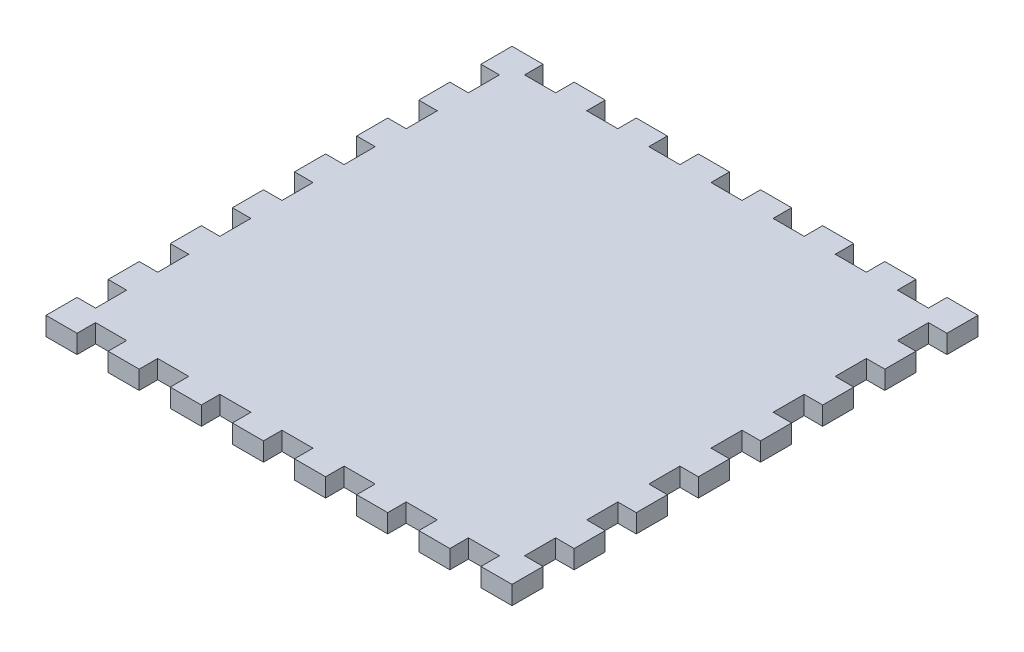
SolidWorks part; units mm, degrees
material "Acrylic (Medium-high impact)"
ref_plane "Front Plane" through (0, 0, 0) normal (0, 0, 1) x (1, 0, 0)
ref_plane "Top Plane" through (0, 0, 0) normal (0, 1, 0) x (1, 0, 0)
ref_plane "Right Plane" through (0, 0, 0) normal (1, 0, 0) x (0, 0, -1)
sketch "Sketch1" plane through (0, 0, 0) normal (0, 1, 0) x (1, 0, 0)
  line L1 (-40, -40) -> (40, -40)
  line L2 (-40, -40) -> (-40, 40)
  line L3 (-40, 40) -> (40, 40)
  line L4 (40, -40) -> (40, 40)
  line L5 (-40, -40) -> (40, 40) construction
  line L6 (-40, 40) -> (40, -40) construction
  point P0 (0, 0)
  dimension "D1" = 80
  dimension "D2" = 80
extrude "Boss-Extrude1" add sketch "Sketch1" along normal blind 3.175
sketch "Sketch2" plane through (0, 3.175, 0) normal (0, 1, 0) x (1, 0, 0)
  line L0 (0, 0) -> (50000, 0) construction
  line L1 (40, -40) -> (40, 40) construction
  line L2 (-34.6667, -40) -> (-34.6667, -36.825)
  line L3 (-40, -40) -> (40, -40) construction
  line L4 (-34.6667, -36.825) -> (-29.3333, -36.825)
  line L5 (-29.3333, -36.825) -> (-29.3333, -40)
  line L6 (-40, 24) -> (-40, 29.3333)
  line L7 (-40, 18.6667) -> (-40, 13.3333)
  line L8 (-24, -40) -> (-24, -36.825)
  line L9 (-24, -36.825) -> (-18.6667, -36.825)
  line L10 (-18.6667, -36.825) -> (-18.6667, -40)
  line L11 (-40, 8) -> (-40, 2.6667)
  line L12 (-13.3333, -40) -> (-13.3333, -36.825)
  line L13 (-13.3333, -36.825) -> (-8, -36.825)
  line L14 (-8, -36.825) -> (-8, -40)
  line L15 (-40, -2.6667) -> (-40, -8)
  line L16 (-2.6667, -40) -> (-2.6667, -36.825)
  line L17 (-2.6667, -36.825) -> (2.6667, -36.825)
  line L18 (2.6667, -36.825) -> (2.6667, -40)
  line L19 (-40, -13.3333) -> (-40, -18.6667)
  line L20 (8, -40) -> (8, -36.825)
  line L21 (8, -36.825) -> (13.3333, -36.825)
  line L22 (13.3333, -36.825) -> (13.3333, -40)
  line L23 (-40, -24) -> (-40, -29.3333)
  line L24 (18.6667, -40) -> (18.6667, -36.825)
  line L25 (18.6667, -36.825) -> (24, -36.825)
  line L26 (24, -36.825) -> (24, -40)
  line L28 (29.3333, -40) -> (29.3333, -36.825)
  line L29 (29.3333, -36.825) -> (34.6667, -36.825)
  line L30 (34.6667, -36.825) -> (34.6667, -40)
  line L33 (34.6667, 36.825) -> (34.6667, 40)
  line L34 (29.3333, 36.825) -> (34.6667, 36.825)
  line L35 (29.3333, 40) -> (29.3333, 36.825)
  line L37 (24, 36.825) -> (24, 40)
  line L38 (18.6667, 36.825) -> (24, 36.825)
  line L39 (18.6667, 40) -> (18.6667, 36.825)
  line L41 (13.3333, 36.825) -> (13.3333, 40)
  line L42 (8, 36.825) -> (13.3333, 36.825)
  line L43 (8, 40) -> (8, 36.825)
  line L45 (2.6667, 36.825) -> (2.6667, 40)
  line L46 (-2.6667, 36.825) -> (2.6667, 36.825)
  line L47 (-2.6667, 40) -> (-2.6667, 36.825)
  line L49 (-8, 36.825) -> (-8, 40)
  line L50 (-13.3333, 36.825) -> (-8, 36.825)
  line L51 (-13.3333, 40) -> (-13.3333, 36.825)
  line L53 (-18.6667, 36.825) -> (-18.6667, 40)
  line L54 (-24, 36.825) -> (-18.6667, 36.825)
  line L55 (-24, 40) -> (-24, 36.825)
  line L58 (-29.3333, 36.825) -> (-29.3333, 40)
  line L59 (-34.6667, 36.825) -> (-29.3333, 36.825)
  line L60 (-34.6667, 40) -> (-34.6667, 36.825)
  line L61 (40, 40) -> (40, 34.6667)
  line L62 (40, 34.6667) -> (36.825, 34.6667)
  line L63 (36.825, 34.6667) -> (36.825, 29.3333)
  line L64 (36.825, 29.3333) -> (40, 29.3333)
  line L66 (40, 34.6667) -> (40, 24)
  line L67 (40, 24) -> (36.825, 24)
  line L69 (36.825, 24) -> (36.825, 18.6667)
  line L70 (36.825, 18.6667) -> (40, 18.6667)
  line L71 (40, 24) -> (40, 13.3333)
  line L72 (40, 13.3333) -> (36.825, 13.3333)
  line L74 (36.825, 13.3333) -> (36.825, 8)
  line L75 (36.825, 8) -> (40, 8)
  line L76 (40, 13.3333) -> (40, 2.6667)
  line L77 (40, 2.6667) -> (36.825, 2.6667)
  line L79 (36.825, 2.6667) -> (36.825, -2.6667)
  line L80 (36.825, -2.6667) -> (40, -2.6667)
  line L81 (40, 2.6667) -> (40, -8)
  line L82 (40, -8) -> (36.825, -8)
  line L84 (36.825, -8) -> (36.825, -13.3333)
  line L85 (36.825, -13.3333) -> (40, -13.3333)
  line L86 (40, -8) -> (40, -18.6667)
  line L87 (40, -18.6667) -> (36.825, -18.6667)
  line L89 (36.825, -18.6667) -> (36.825, -24)
  line L90 (36.825, -24) -> (40, -24)
  line L91 (40, -18.6667) -> (40, -29.3333)
  line L92 (40, -29.3333) -> (36.825, -29.3333)
  line L93 (40, -29.3333) -> (40, -34.6667)
  line L94 (36.825, -29.3333) -> (36.825, -34.6667)
  line L95 (36.825, -34.6667) -> (40, -34.6667)
  line L96 (40, -34.6667) -> (40, -40)
  line L97 (0, 0) -> (0, 50000) construction
  line L98 (40, 40) -> (-40, 40) construction
  line L99 (0, 0) -> (-50000, 0) construction
  line L100 (-40, -34.6667) -> (-40, -40)
  line L101 (-36.825, -34.6667) -> (-40, -34.6667)
  line L102 (-36.825, -29.3333) -> (-36.825, -34.6667)
  line L103 (-40, -29.3333) -> (-40, -34.6667)
  line L104 (-40, -29.3333) -> (-36.825, -29.3333)
  line L105 (-40, -18.6667) -> (-40, -29.3333)
  line L106 (-36.825, -24) -> (-40, -24)
  line L107 (-36.825, -18.6667) -> (-36.825, -24)
  line L109 (-40, -18.6667) -> (-36.825, -18.6667)
  line L110 (-40, -8) -> (-40, -18.6667)
  line L111 (-36.825, -13.3333) -> (-40, -13.3333)
  line L112 (-36.825, -8) -> (-36.825, -13.3333)
  line L114 (-40, -8) -> (-36.825, -8)
  line L115 (-40, 2.6667) -> (-40, -8)
  line L116 (-36.825, -2.6667) -> (-40, -2.6667)
  line L117 (-36.825, 2.6667) -> (-36.825, -2.6667)
  line L119 (-40, 2.6667) -> (-36.825, 2.6667)
  line L120 (-40, 13.3333) -> (-40, 2.6667)
  line L121 (-36.825, 8) -> (-40, 8)
  line L122 (-36.825, 13.3333) -> (-36.825, 8)
  line L124 (-40, 13.3333) -> (-36.825, 13.3333)
  line L125 (-40, 24) -> (-40, 13.3333)
  line L126 (-36.825, 18.6667) -> (-40, 18.6667)
  line L127 (-36.825, 24) -> (-36.825, 18.6667)
  line L129 (-40, 24) -> (-36.825, 24)
  line L130 (-40, 34.6667) -> (-40, 24)
  line L131 (-36.825, 29.3333) -> (-40, 29.3333)
  line L133 (-36.825, 34.6667) -> (-36.825, 29.3333)
  line L134 (-40, 34.6667) -> (-36.825, 34.6667)
  line L135 (-40, 40) -> (-40, 34.6667)
  line L136 (40, 29.3333) -> (40, 24) [skipped]
  line L137 (40, 18.6667) -> (40, 13.3333) [skipped]
  line L138 (40, 8) -> (40, 2.6667) [skipped]
  line L139 (40, -2.6667) -> (40, -8) [skipped]
  line L140 (40, -13.3333) -> (40, -18.6667) [skipped]
  line L141 (40, -24) -> (40, -29.3333) [skipped]
  line L142 (-40, 40) -> (40, 40)
  line L143 (-40, -40) -> (40, -40)
  point P5 (40, 0)
  point P110 (0, 40)
  line M33 (-40, 40) -> (-40, -40)
  line M34 (-40, -40) -> (40, -40)
  dimension "D1" = 3.175
  dimension "D4" = 7
  dimension "D6" = 7
extrude "Cut-Extrude3" cut sketch "Sketch2" against normal through all flip side to cut contours L134 L133 L131 L130 L129 L127 L126 L125 L124 L122 L121 L120 L119 L117 L116 L115 L114 L112 L111 L110 L109 L107 L106 L105 L104 L102 L101 L2 L4 L5 L8 L9 L10 L12 L13 L14 L16 L17 L18 L20 L21 L22 L24 M33 M34 region at (0, 3.175, 0)
